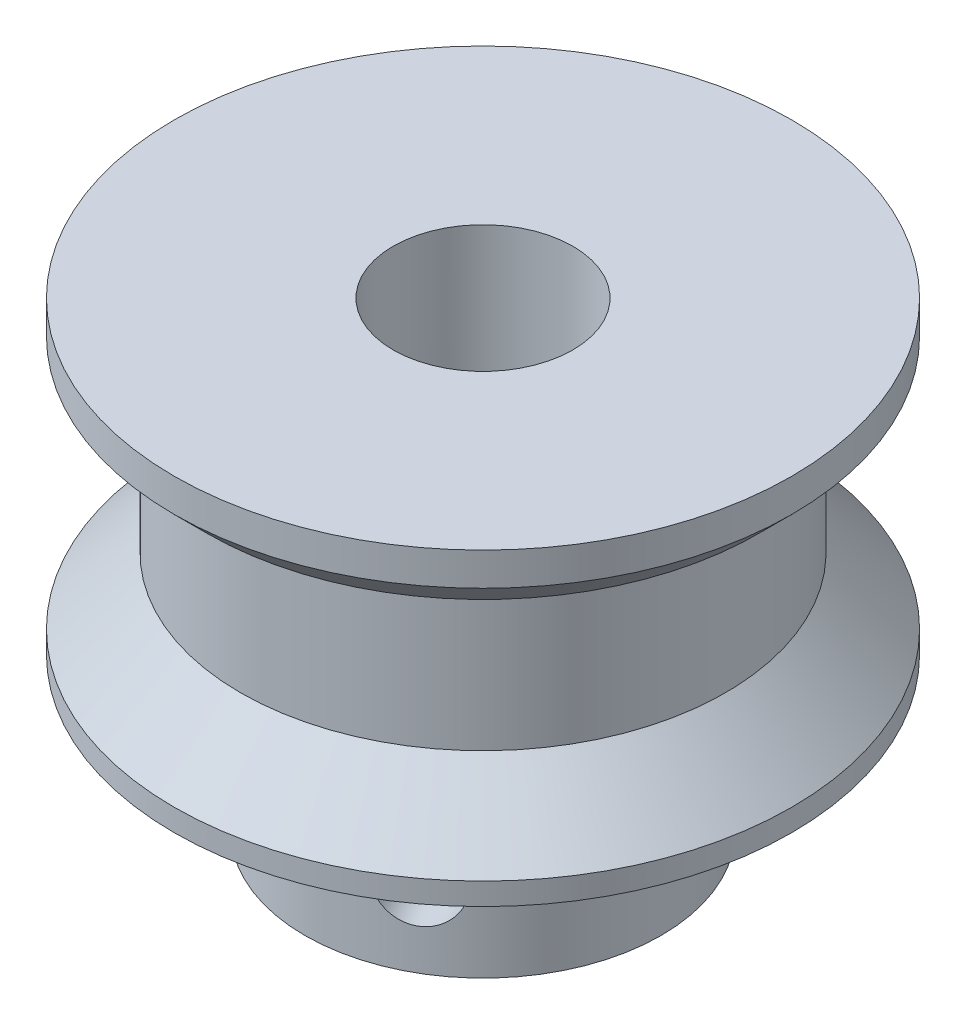
SolidWorks part; units mm, degrees
ref_plane "Plan de face" through (0, 0, 0) normal (0, 0, 1) x (1, 0, 0)
ref_plane "Plan de dessus" through (0, 0, 0) normal (0, 1, 0) x (1, 0, 0)
ref_plane "Plan de droite" through (0, 0, 0) normal (1, 0, 0) x (0, 0, -1)
sketch "Esquisse1" plane through (0, 0, 0) normal (0, 1, 0) x (1, 0, 0)
  circle A0 centre (0, 0) radius 4.075
  circle A1 centre (0, 0) radius 6
  dimension "D1" = 8.15
  dimension "D2" = 12
extrude "Boss.-Extru.1" add sketch "Esquisse1" along normal blind 2
sketch "Esquisse2" plane through (0, 0, 0) normal (0, -1, 0) x (1, 0, 0)
  circle A0 centre (0, 0) radius 4.075
  circle A1 centre (0, 0) radius 8.075
  point P4 (0, 0)
  dimension "D1" = 4
extrude "Boss.-Extru.2" add sketch "Esquisse2" along normal blind 7
sketch "Esquisse3" plane through (0, 0, 0) normal (0, 1, 0) x (1, 0, 0)
  circle A0 centre (0, 0) radius 11
  circle A2 centre (0, 0) radius 8.075 construction
  dimension "D1" = 22
extrude "Boss.-Extru.3" add sketch "Esquisse3" along normal blind 7 from offset 4
sketch "Esquisse4" plane through (0, 0, 0) normal (0, 1, 0) x (1, 0, 0)
  circle A0 centre (0, 0) radius 6
  circle A1 centre (0, 0) radius 14
  point P5 (0, 0)
  dimension "D1" = 28
extrude "Boss.-Extru.4" add sketch "Esquisse4" along normal up to surface (4 mm away) up to face at (0, 4, 11)
sketch "Esquisse5" plane through (0, 11, 0) normal (0, 1, 0) x (1, 0, 0)
  circle A5 centre (0, 0) radius 14
  circle A7 centre (0, 0) radius 14 construction
extrude "Boss.-Extru.5" add sketch "Esquisse5" along normal blind 3
chamfer "Chanfrein1" distance 3 angle 45 1 edges at (0, 4, 14)
sketch "Esquisse6" plane through (0, 4, 0) normal (0, -1, 0) x (1, 0, 0)
  circle A0 centre (0, 0) radius 4.075
extrude "Enlèv. mat.-Extru.1" cut sketch "Esquisse6" against normal up to next
sketch "Esquisse7" plane through (0, 0, 0) normal (1, 0, 0) x (0, 0, -1)
  line L0 (0, -7) -> (0, 0) construction
  line L1 (-8.075, -7) -> (8.075, -7) construction
  circle A0 centre (0, -3.5) radius 1.65
  point P5 (0, -8.6439)
  point P8 (0, 0)
  point P9 (0, 0)
  point P10 (0, 0)
  dimension "D1" = 3.3
extrude "Enlèv. mat.-Extru.2" cut sketch "Esquisse7" against normal up to next
pattern_circular "Répétition circulaire1" count 3 every 120 about axis through (0, -7, 0) along (0, 1, 0) of "Enlèv. mat.-Extru.2" reverse direction yes
fillet "Congé1" radius 1 1 edges at (0, -7, -4.075)
chamfer "Chanfrein2" distance 1.5 angle 45 1 edges at (0, 11, 14)
sketch "Esquisse8" plane through (0, 4, 0) normal (0, -1, 0) x (1, 0, 0)
  circle A0 centre (0, 0) radius 4.075
  circle A1 centre (0, 0) radius 6
extrude "Boss.-Extru.6" add sketch "Esquisse8" along normal up to next
